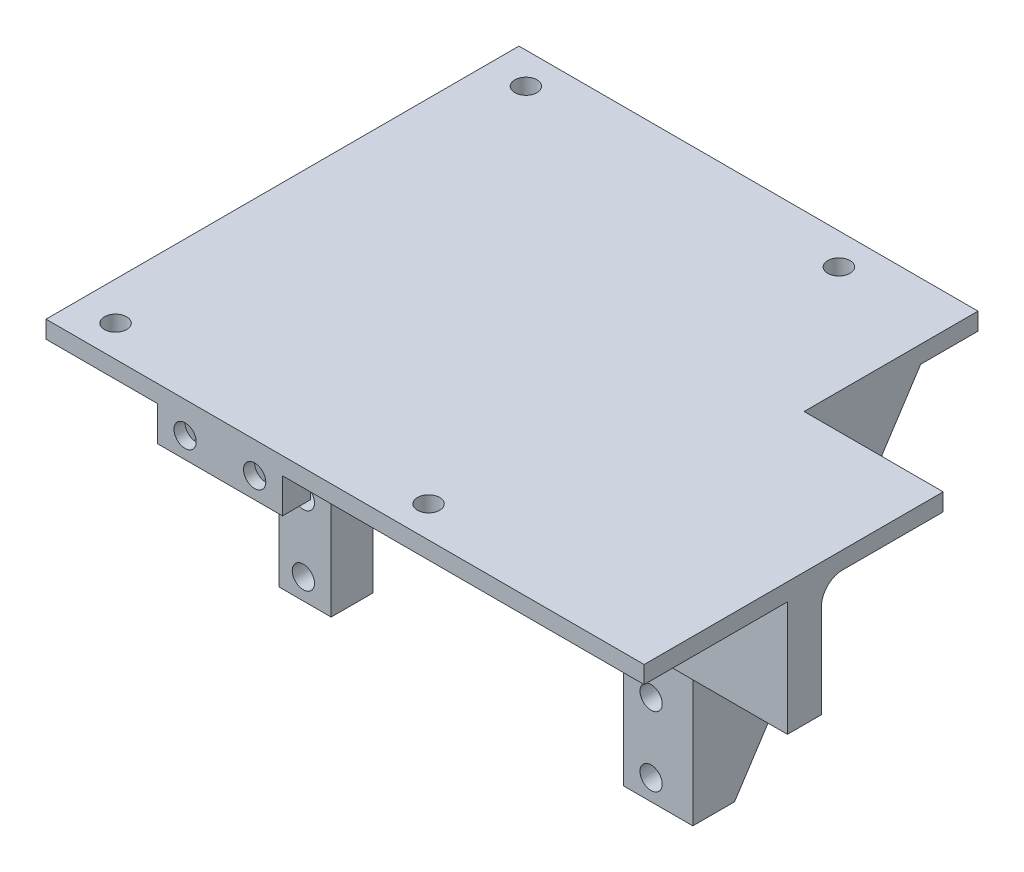
SolidWorks part; units mm, degrees
ref_plane "前视基准面" through (0, 0, 0) normal (0, 0, 1) x (1, 0, 0)
ref_plane "上视基准面" through (0, 0, 0) normal (0, 1, 0) x (1, 0, 0)
ref_plane "右视基准面" through (0, 0, 0) normal (1, 0, 0) x (0, 0, -1)
other "Configuration Table"
sketch "Orthogonal chassis plate primary profile" plane through (0, 0, 0) normal (0, 0, 1) x (1, 0, 0)
  line L0 (-25, 29) -> (41, 29)
  line L1 (41, 29) -> (41, 33)
  line L2 (41, 33) -> (-25, 33)
  line L3 (-25, 33) -> (-25, 29)
extrude "Orthogonal chassis plate primary" add sketch "Orthogonal chassis plate primary profile" along normal blind 25.1 from offset 15 offset against normal yes
sketch "Orthogonal chassis plate guide side profile" plane through (0, 0, 0) normal (0, 0, 1) x (1, 0, 0)
  line L0 (-25, 29) -> (84, 29)
  line L1 (84, 29) -> (84, 33)
  line L2 (84, 33) -> (-25, 33)
  line L3 (-25, 33) -> (-25, 29)
extrude "Orthogonal chassis plate guide side" add sketch "Orthogonal chassis plate guide side profile" along normal blind 43 from offset 10
sketch "Horizontal servo seat uprights profile" plane through (0, 0, 0) normal (0, 0, 1) x (1, 0, 0)
  line L0 (-18.5, -8) -> (-11, -8)
  line L1 (-11, -8) -> (-11, 29.1)
  line L2 (-11, 29.1) -> (-18.5, 29.1)
  line L4 (31, -8) -> (41, -8)
  line L5 (41, -8) -> (41, 29.1)
  line L6 (41, 29.1) -> (31, 29.1)
  line L7 (31, 29.1) -> (31, -8)
  line L12 (-18.5, 29.1) -> (-18.5, -8)
extrude "Horizontal servo seat uprights" add sketch "Horizontal servo seat uprights profile" along normal blind 6 from offset 20
sketch "Side mounting face for MGN7 rail profile" plane through (0, 0, 0) normal (0, 0, 1) x (1, 0, 0)
  line L0 (-17, 12.5) -> (83, 12.5)
  line L1 (83, 12.5) -> (83, 29.1)
  line L2 (83, 29.1) -> (-17, 29.1)
  line L3 (-17, 29.1) -> (-17, 12.5)
extrude "Side mounting face for MGN7 rail" add sketch "Side mounting face for MGN7 rail profile" along normal blind 4.9 from offset 27.5
sketch "Horizontal limit bracket foot support profile" plane through (0, 0, 0) normal (0, 0, 1) x (1, 0, 0)
  line L0 (-9, 24) -> (9, 24)
  line L1 (9, 24) -> (9, 29.1)
  line L2 (9, 29.1) -> (-9, 29.1)
  line L3 (-9, 29.1) -> (-9, 24)
extrude "Horizontal limit bracket foot support" add sketch "Horizontal limit bracket foot support profile" along normal blind 4 from offset 49
sketch "Chassis mounting hole layout 45 x 41 mm profile" plane through (0, 0, 0) normal (0, 1, 0) x (1, 0, 0)
  circle A0 centre (-19.5, 10.5) radius 1.6
  circle A1 centre (-19.5, -48.5) radius 1.6
  circle A2 centre (25.5, 10.5) radius 1.6
  circle A3 centre (25.5, -48.5) radius 1.6
  circle A4 centre (70.5, -48.5) radius 1.6
  point P12 (-24.5, 14.5)
  dimension "D3" = 3.2
  dimension "D6" = 2
  dimension "D9" = 3.2
  dimension "D5" = 59
  dimension "D1" = 5
  dimension "D2" = 4
  dimension "D4" = 2
  dimension "D7" = 50
  dimension "D8" = 4
extrude "Chassis mounting hole layout 45 x 41 mm" cut sketch "Chassis mounting hole layout 45 x 41 mm profile" along normal blind 4.2 from offset 28.9
sketch "Servo mount 50 x 10 mm pitch profile" plane through (0, 0, 0) normal (0, 0, 1) x (1, 0, 0)
  circle A0 centre (-15, -5) radius 1.6
  circle A1 centre (-15, 5) radius 1.6
  circle A2 centre (35, -5) radius 1.6
  circle A3 centre (35, 5) radius 1.6
  point P8 (-21, -8)
  dimension "D3" = 3.2
  dimension "D6" = 3.2
  dimension "D9" = 3.2
  dimension "D12" = 3.2
  dimension "D1" = 6
  dimension "D2" = 3
  dimension "D4" = 6
  dimension "D5" = 13
  dimension "D7" = 56
  dimension "D8" = 3
  dimension "D10" = 56
  dimension "D11" = 13
extrude "Servo mount 50 x 10 mm pitch" cut sketch "Servo mount 50 x 10 mm pitch profile" along normal blind 6.2 from offset 19.9
sketch "Guide M2 mounting pilots 15 mm pitch profile" plane through (0, 0, 0) normal (0, 0, 1) x (1, 0, 0)
  circle A0 centre (-12, 19) radius 1.05
  circle A1 centre (3, 19) radius 1.05
  circle A2 centre (18, 19) radius 1.05
  circle A3 centre (33, 19) radius 1.05
  circle A4 centre (48, 19) radius 1.05
  circle A5 centre (63, 19) radius 1.05
  circle A6 centre (78, 19) radius 1.05
  point P14 (-17, 12)
  dimension "D3" = 2.1
  dimension "D6" = 2.1
  dimension "D9" = 2.1
  dimension "D12" = 2.1
  dimension "D15" = 2.1
  dimension "D18" = 2.1
  dimension "D21" = 2.1
  dimension "D1" = 5
  dimension "D2" = 7
  dimension "D4" = 20
  dimension "D5" = 7
  dimension "D7" = 35
  dimension "D8" = 7
  dimension "D10" = 50
  dimension "D11" = 7
  dimension "D13" = 65
  dimension "D14" = 7
  dimension "D16" = 80
  dimension "D17" = 7
  dimension "D19" = 95
  dimension "D20" = 7
extrude "Guide M2 mounting pilots 15 mm pitch" cut sketch "Guide M2 mounting pilots 15 mm pitch profile" along normal blind 5.05 from offset 27.45
sketch "Stop mounting two M3 pilots 10 mm pitch profile" plane through (0, 0, 0) normal (0, 0, 1) x (1, 0, 0)
  circle A0 centre (-5, 27) radius 1.6
  circle A1 centre (5, 27) radius 1.6
  point P4 (-9, 24)
  dimension "D3" = 3.2
  dimension "D6" = 3.2
  dimension "D1" = 4
  dimension "D2" = 3
  dimension "D4" = 14
  dimension "D5" = 3
extrude "Stop mounting two M3 pilots 10 mm pitch" cut sketch "Stop mounting two M3 pilots 10 mm pitch profile" along normal blind 4.2 from offset 48.9
fillet "圆角2" radius 3 1 edges at (33, 29, 27.5)
sketch "草图3" plane through (0, 29, 0) normal (0, -1, 0) x (-1, 0, 0)
  line L0 (9, -49) -> (-9, -49) construction
  line L1 (9, -49) -> (-9, -49)
  line L2 (9, -49) -> (9, -46)
  line L3 (9, -46) -> (-9, -46)
  line L4 (-9, -49) -> (-9, -46)
  line L5 (9, -53) -> (9, -49) construction
  dimension "D1" = 18
  dimension "D2" = 3
extrude "切除-拉伸1" cut sketch "草图3" against normal blind 2
sketch "草图4" plane through (0, 0, 49) normal (0, 0, -1) x (-1, 0, 0)
  line L0 (9, 24) -> (-9, 24) construction
  line L1 (-3.2679, 30) -> (-6.7321, 30)
  line L2 (-6.7321, 30) -> (-8.4641, 27)
  line L3 (-8.4641, 27) -> (-6.7321, 24)
  line L4 (-6.7321, 24) -> (-3.2679, 24)
  line L5 (-3.2679, 24) -> (-1.5359, 27)
  line L6 (-1.5359, 27) -> (-3.2679, 30)
  line L7 (6.7321, 30) -> (3.2679, 30)
  line L8 (3.2679, 30) -> (1.5359, 27)
  line L9 (1.5359, 27) -> (3.2679, 24)
  line L10 (3.2679, 24) -> (6.7321, 24)
  line L11 (6.7321, 24) -> (8.4641, 27)
  line L12 (8.4641, 27) -> (6.7321, 30)
  circle A0 centre (-5, 27) radius 3 construction
  circle A1 centre (5, 27) radius 3 construction
  dimension "D1" = 6
  dimension "D2" = 3
extrude "切除-拉伸2" cut sketch "草图4" against normal blind 2.4
sketch "草图5" plane through (-11, 0, 0) normal (1, 0, 0) x (0, 0, -1)
  line L0 (-20, 29) -> (5, 29)
  line L1 (-10, 29) -> (15, 29) construction
  line L2 (5, 29) -> (-20, 9)
  line L3 (-20, -8) -> (-20, 29) construction
  line L4 (-20, 9) -> (-20, 29)
  dimension "D1" = 25
  dimension "D2" = 20
extrude "凸台-拉伸3" add sketch "草图5" against normal blind 7.5
sketch "草图6" plane through (31, 0, 0) normal (-1, 0, 0) x (0, 0, 1)
  line L0 (20, 29) -> (-5, 29)
  line L1 (-5, 29) -> (20, 9)
  line L2 (20, 29) -> (20, -8) construction
  line L3 (20, 9) -> (20, 29)
  dimension "D1" = 25
  dimension "D2" = 20
extrude "凸台-拉伸4" add sketch "草图6" against normal blind 10
fillet "圆角3" radius 5 4 edges at (36, 29, -5) (-14.75, 29, -5) (-14.75, 9, 20) (36, 9, 20)
sketch "草图7" plane through (0, 0, 53) normal (0, 0, 1) x (1, 0, 0)
  line L0 (84, 29) -> (84, 33) construction
  line L1 (-25, 33) -> (84, 33)
  line L2 (-25, 33) -> (-25, 31.5)
  line L3 (-25, 31.5) -> (84, 31.5)
  line L4 (84, 33) -> (84, 31.5)
  dimension "D1" = 1.5
extrude "切除-拉伸3" cut sketch "草图7" against normal blind 80
sketch "草图8" plane through (0, 31.5, 0) normal (0, 1, 0) x (1, 0, 0)
  line L0 (-25, -53) -> (84, -53) construction
  line L1 (84, -10) -> (61, -10)
  line L2 (84, -10) -> (84, -53)
  line L3 (84, -53) -> (61, -53)
  line L4 (61, -10) -> (61, -53)
  dimension "D1" = 23
extrude "切除-拉伸4" cut sketch "草图8" against normal blind 30
sketch "Raise servo mounting tabs by 4.10 mm profile" plane through (0, 0, 0) normal (0, 0, 1) x (1, 0, 0)
  line L0 (-18.5, -12.1) -> (-11, -12.1)
  line L1 (-11, -12.1) -> (-11, -7)
  line L2 (-11, -7) -> (-18.5, -7)
  line L3 (-18.5, -7) -> (-18.5, -12.1)
  line L4 (31, -12.1) -> (41, -12.1)
  line L5 (41, -12.1) -> (41, -7)
  line L6 (41, -7) -> (31, -7)
  line L7 (31, -7) -> (31, -12.1)
extrude "Raise servo mounting tabs by 4.10 mm" add sketch "Raise servo mounting tabs by 4.10 mm profile" along normal blind 6 from offset 20
sketch "Fill original servo holes profile" plane through (0, 0, 0) normal (0, 0, 1) x (1, 0, 0)
  circle A0 centre (-15, -5) radius 1.65
  circle A1 centre (-15, 5) radius 1.65
  circle A2 centre (35, -5) radius 1.65
  circle A3 centre (35, 5) radius 1.65
extrude "Fill original servo holes" add sketch "Fill original servo holes profile" along normal blind 6 from offset 20
sketch "Servo mounting holes raised 4.10 mm profile" plane through (0, 0, 0) normal (0, 0, 1) x (1, 0, 0)
  circle A0 centre (-15, -9.1) radius 1.6
  circle A1 centre (-15, 0.9) radius 1.6
  circle A2 centre (35, -9.1) radius 1.6
  circle A3 centre (35, 0.9) radius 1.6
extrude "Servo mounting holes raised 4.10 mm" cut sketch "Servo mounting holes raised 4.10 mm profile" along normal blind 6.2 from offset 19.9
sketch "草图9" plane through (41, 0, 0) normal (1, 0, 0) x (0, 0, -1)
  line L0 (-24.5, 29) -> (6.7539, 29)
  line L1 (6.7539, 29) -> (-20, -12.1)
  line L2 (-20, -12.1) -> (-24.5, 29)
extrude "凸台-拉伸5" add sketch "草图9" against normal blind 2
